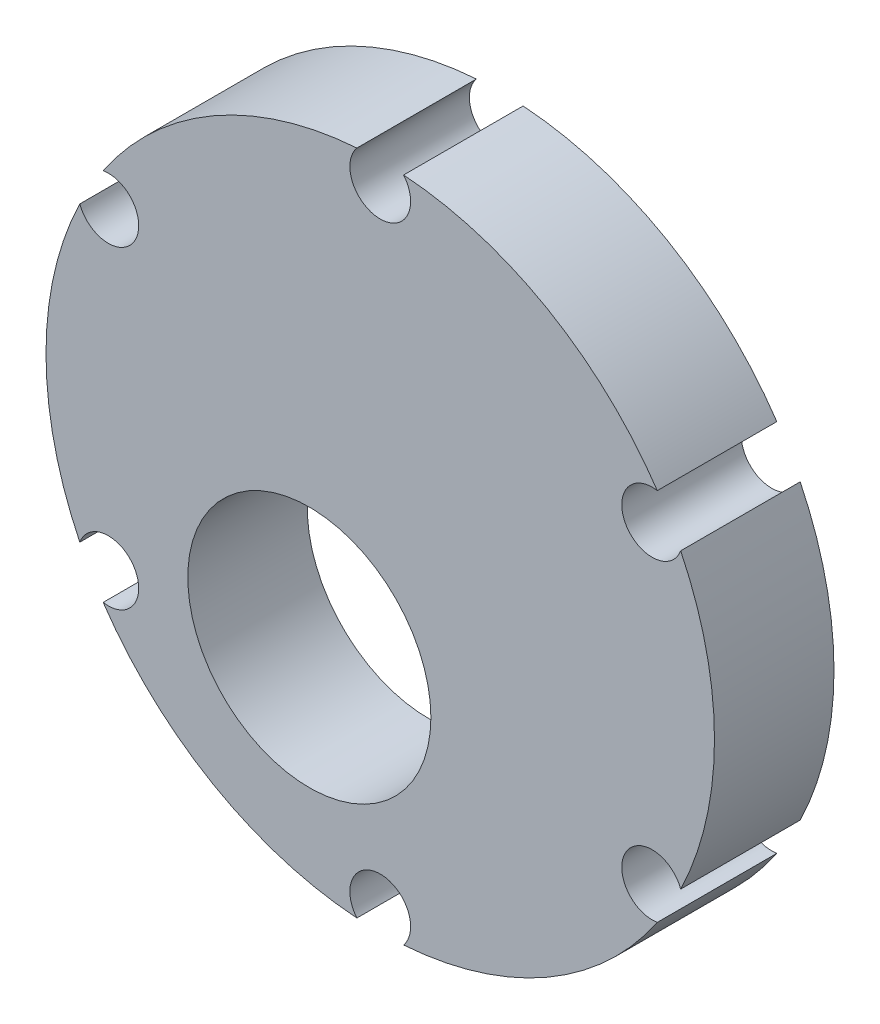
SolidWorks part; units mm, degrees
ref_plane "Front Plane" through (0, 0, 0) normal (0, 0, 1) x (1, 0, 0)
ref_plane "Top Plane" through (0, 0, 0) normal (0, 1, 0) x (1, 0, 0)
ref_plane "Right Plane" through (0, 0, 0) normal (1, 0, 0) x (0, 0, -1)
sketch "Sketch1" plane through (0, 0, 0) normal (0, 0, 1) x (1, 0, 0)
  circle A0 centre (0, 0) radius 16.5
  dimension "D1" = 33
extrude "Boss-Extrude1" add sketch "Sketch1" along normal blind 5.9
sketch "Sketch2" plane through (0, 0, 5.9) normal (0, 0, 1) x (1, 0, 0)
  circle A0 centre (0, 15.5) radius 1.5
  circle A1 centre (13.4234, 7.75) radius 1.5
  circle A2 centre (13.4234, -7.75) radius 1.5
  circle A3 centre (0, -15.5) radius 1.5
  circle A4 centre (-13.4234, -7.75) radius 1.5
  circle A5 centre (-13.4234, 7.75) radius 1.5
  point P15 (0, 0)
  dimension "D1" = 3
  dimension "D2" = 15.5
  dimension "D3" = 6
extrude "Cut-Extrude1" cut sketch "Sketch2" against normal through all
sketch "Sketch3" plane through (0, 0, 5.9) normal (0, 0, 1) x (1, 0, 0)
  line L0 (-3.5, -6.0622) -> (0, 0) construction
  line L1 (0, 0) -> (0, -15.5) construction
  circle A0 centre (-3.5, -6.0622) radius 6
  dimension "D1" = 12
  dimension "D2" = 30
  dimension "D3" = 7
extrude "Cut-Extrude2" cut sketch "Sketch3" against normal through all
equation "\"smallPulleyTeeth\"= 15"
equation "\"largePulleyTeeth\"= 30"
equation "\"eighthThick\"= 2.9mm"
equation "\"sixteenthThick\" = 1.7mm"
equation "\"wheelEighthThick\"=3.0mm"
equation "\"quarterThick\"=5.9mm"
equation "\"OD\" = 145mm"
equation "\"puckAngle\" = 60.5deg"
equation "\"puckDiam\" = 76.5mm"
equation "\"axlePress\" = 5.9mm"
equation "\"D1@Boss-Extrude1\"=\"quarterThick\""
